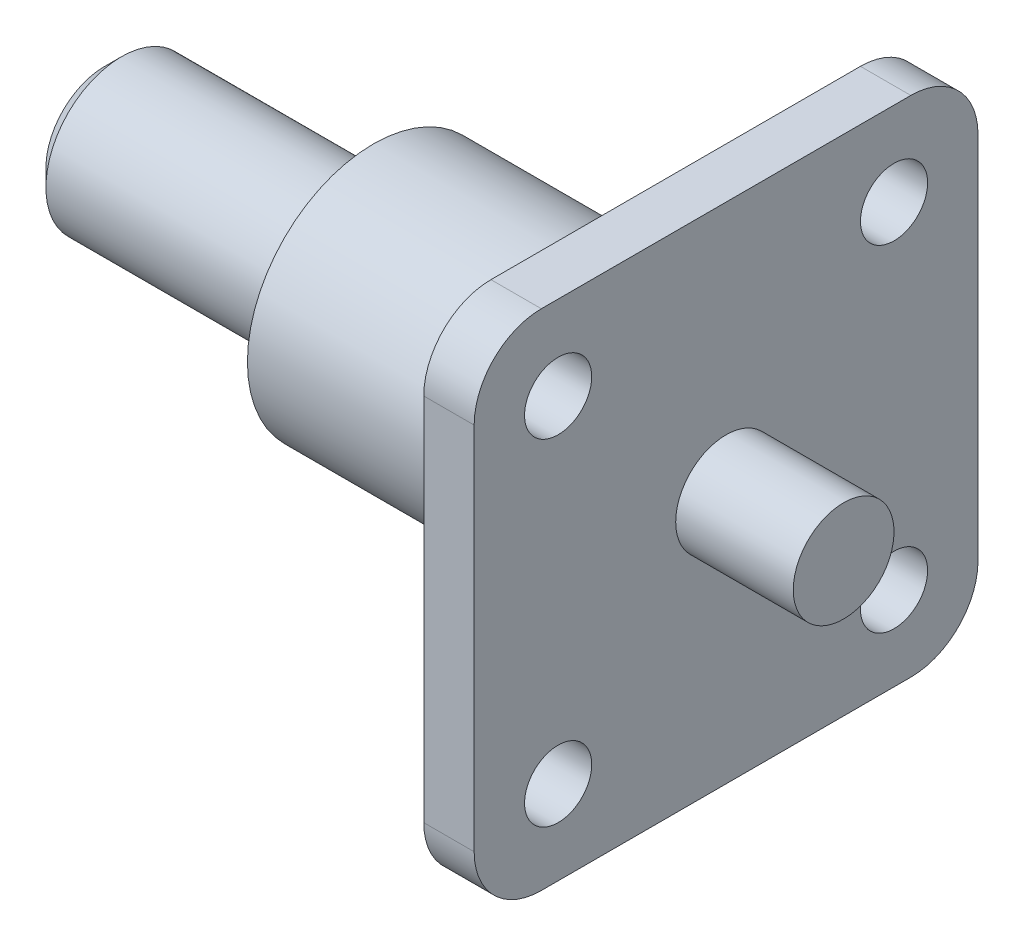
SolidWorks part; units mm, degrees
ref_plane "Alzado" through (0, 0, 0) normal (0, 0, 1) x (1, 0, 0)
ref_plane "Planta" through (0, 0, 0) normal (0, 1, 0) x (1, 0, 0)
ref_plane "Vista lateral" through (0, 0, 0) normal (1, 0, 0) x (0, 0, -1)
sketch "Croquis1" plane through (0, 0, 0) normal (0, 0, 1) x (1, 0, 0)
  line L0 (-18.3711, 0) -> (42.3295, 0) construction
  line L1 (-16, 0) -> (-16, 4.5)
  line L2 (-16, 4.5) -> (0, 4.5)
  line L3 (0, 4.5) -> (0, 7.5)
  line L4 (0, 7.5) -> (18, 7.5)
  line L5 (18, 7.5) -> (18, 0) construction
  line L6 (-16, 0) -> (28, 0)
  line L7 (18, 7.5) -> (18, 3)
  line L8 (18, 3) -> (28, 3)
  line L9 (28, 3) -> (28, 0)
  line L10 (0, 0) -> (0, 8.1876) construction
  point P9 (0, 6)
  dimension "D1" = 9
  dimension "D2" = 15
  dimension "D3" = 16
  dimension "D4" = 18
  dimension "D5" = 6
  dimension "D6" = 10
revolve "Revolución1" add sketch "Croquis1" angle 360 about L0
fillet "Redondeo1" radius 1 1 edges at (0, 0, 4.5)
chamfer "Chaflán1" distance 1 angle 45 1 edges at (-16, 0, 4.5)
sketch "Croquis2" plane through (18, 0, 0) normal (1, 0, 0) x (0, 0, -1)
  line L1 (-11, -15) -> (11, -15)
  line L2 (-15, -11) -> (-15, 11)
  line L3 (-11, 15) -> (11, 15)
  line L4 (15, -11) -> (15, 11)
  line L5 (-15, -15) -> (15, 15) construction
  line L6 (-15, 15) -> (15, -15) construction
  line L7 (-10, -10) -> (10, -10) construction
  line L8 (-10, -10) -> (-10, 10) construction
  line L9 (-10, 10) -> (10, 10) construction
  line L10 (10, -10) -> (10, 10) construction
  line L11 (-10, -10) -> (10, 10) construction
  line L12 (-10, 10) -> (10, -10) construction
  circle A0 centre (-10, 10) radius 2
  circle A1 centre (10, 10) radius 2
  circle A2 centre (10, -10) radius 2
  circle A3 centre (-10, -10) radius 2
  arc A4 (-11, -15) -> (-15, -11) centre (-11, -11) cw
  arc A5 (11, -15) -> (15, -11) centre (11, -11) ccw
  arc A6 (11, 15) -> (15, 11) centre (11, 11) cw
  arc A7 (-15, 11) -> (-11, 15) centre (-11, 11) cw
  point P0 (0, 0)
  point P5 (0, 0)
  dimension "D4" = 4
  dimension "D5" = 4
  dimension "D1" = 30
  dimension "D2" = 30
  dimension "D3" = 20
extrude "Saliente-Extruir1" add sketch "Croquis2" along normal blind 3
